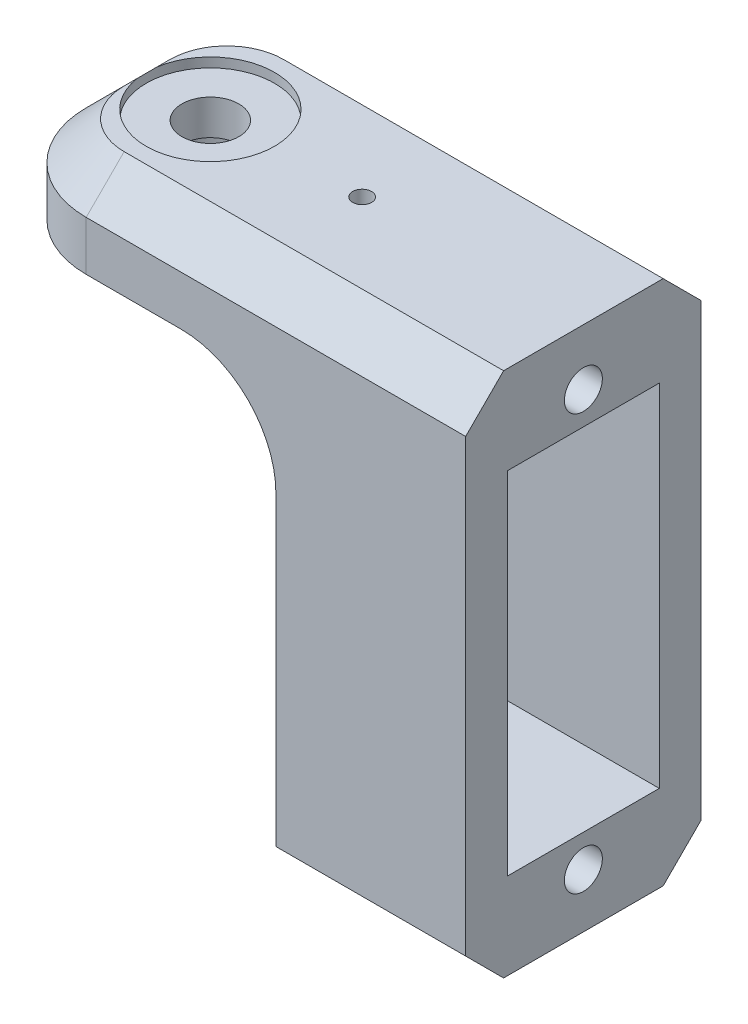
SolidWorks part; units mm, degrees
ref_plane "前视基准面" through (0, 0, 0) normal (0, 0, 1) x (1, 0, 0)
ref_plane "上视基准面" through (0, 0, 0) normal (0, 1, 0) x (1, 0, 0)
ref_plane "右视基准面" through (0, 0, 0) normal (1, 0, 0) x (0, 0, -1)
sketch "Sketch1" plane through (0, 0, 0) normal (1, 0, 0) x (0, 0, -1)
  line L8 (5.2335, 19.0932) -> (-2.7665, 19.0932)
  line L9 (5.2335, 19.0932) -> (5.2335, 0.5932)
  line L10 (5.2335, 0.5932) -> (-2.7665, 0.5932)
  line L11 (-2.7665, 19.0932) -> (-2.7665, 0.5932)
  line L12 (5.2335, 19.0932) -> (-2.7665, 0.5932) construction
  line L13 (-4.9711, 23.759) -> (7.4381, 23.759)
  line L14 (-4.9711, 23.759) -> (-4.9711, -3.9595)
  line L15 (-4.9711, -3.9595) -> (7.4381, -3.9595)
  line L16 (7.4381, 23.759) -> (7.4381, -3.9595)
  line L17 (5.2335, 0.5932) -> (-2.7665, 19.0932) construction
  line L18 (2.0348, 20.7982) -> (0.4322, 20.7982) construction
  line L19 (2.0348, 20.7982) -> (2.0348, -1.1118) construction
  line L20 (2.0348, -1.1118) -> (0.4322, -1.1118) construction
  line L21 (0.4322, 20.7982) -> (0.4322, -1.1118) construction
  line L22 (2.0348, 20.7982) -> (0.4322, -1.1118) construction
  line L23 (2.0348, -1.1118) -> (0.4322, 20.7982) construction
  circle A4 centre (1.2335, 20.7982) radius 1
  circle A5 centre (1.2335, -1.1118) radius 1
  point P0 (1.2335, 9.8432)
  point P6 (1.2335, 9.8432)
  dimension "D1" = 8
  dimension "D2" = 18.5
  dimension "D3" = 21.91
  dimension "D4" = 0
  dimension "D5" = 0
extrude "Boss-Extrude1" add sketch "Sketch1" along normal blind 10
sketch "Sketch6" plane through (0, 0, 0) normal (-1, 0, 0) x (0, 0, 1)
  line L0 (4.9711, 23.759) -> (4.9711, -3.9595) construction
  line L1 (-7.4381, 23.759) -> (4.9711, 23.759)
  line L2 (-7.4381, 23.759) -> (-7.4381, 19.1557)
  line L3 (-7.4381, 19.1557) -> (4.9711, 19.1557)
  line L4 (4.9711, 23.759) -> (4.9711, 19.1557)
extrude "Boss-Extrude3" add sketch "Sketch6" along normal blind 15
sketch "Sketch7" plane through (0, 19.1557, 0) normal (0, -1, 0) x (1, 0, 0)
  line L0 (-15, -1.2335) -> (-14.2376, -1.2335) construction
  circle A0 centre (-9.66, -1.2335) radius 3.1
  dimension "D1" = 6.2
extrude "Cut-Extrude4" cut sketch "Sketch7" against normal blind 2.25
sketch "Sketch8" plane through (0, 19.1557, 0) normal (0, -1, 0) x (1, 0, 0)
  line L0 (0, -13.6427) -> (0, 11.1757) construction
  line L1 (-11.3232, 0.6966) -> (0, 0.6966)
  line L2 (-11.3232, 0.6966) -> (-11.3232, -3.3034)
  line L3 (-11.3232, -3.3034) -> (0, -3.3034)
  line L4 (0, 0.6966) -> (0, -3.3034)
  circle A0 centre (-9.66, -1.2335) radius 3.1 construction
  circle A1 centre (-9.66, -1.2335) radius 3.1 construction
  point P0 (-6.6347, -1.9098)
  dimension "D1" = 4
extrude "Cut-Extrude5" cut sketch "Sketch8" against normal blind 1.25
sketch "Sketch9" plane through (0, 21.4057, 0) normal (0, -1, 0) x (1, 0, 0)
  circle A0 centre (-9.66, -1.2335) radius 1.5
  circle A1 centre (-1.66, -1.2335) radius 0.5
  dimension "D1" = 1
  dimension "D2" = 3
  dimension "D3" = 8
extrude "Cut-Extrude7" cut sketch "Sketch9" against normal through all both and the other way through all
fillet "Fillet2" radius 5 2 edges at (-15, 21.4574, -7.4381) (-15, 21.4574, 4.9711)
sketch "Sketch10" plane through (0, 23.759, 0) normal (0, 1, 0) x (1, 0, 0)
  circle A0 centre (-9.66, 1.2335) radius 3.3804
extrude "Cut-Extrude8" cut sketch "Sketch10" against normal blind 0.5
chamfer "Chamfer3" distance 2 angle 45 7 edges at (0, 23.759, -7.4381) (-13.5355, 23.759, -5.9737) (-15, 23.759, -1.2335) (-13.5355, 23.759, 3.5066) (0, 23.759, 4.9711) (5, -3.9595, -7.4381) (5, -3.9595, 4.9711)
fillet "Fillet3" radius 5 2 edges at (0, 19.1557, -5.3708) (0, 19.1557, 2.8338)
